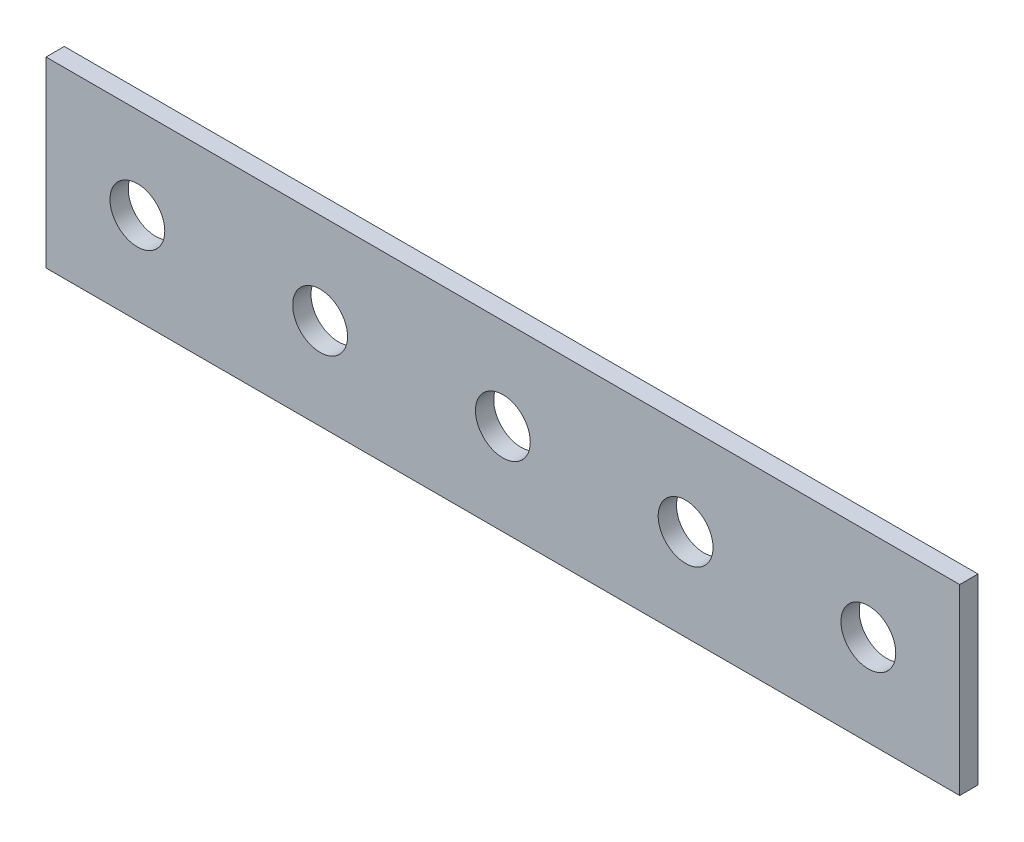
SolidWorks part; units mm, degrees
ref_plane "Front Plane" through (0, 0, 0) normal (0, 0, 1) x (1, 0, 0)
ref_plane "Top Plane" through (0, 0, 0) normal (0, 1, 0) x (1, 0, 0)
ref_plane "Right Plane" through (0, 0, 0) normal (1, 0, 0) x (0, 0, -1)
sketch "Esquisse1" plane through (0, 0, 0) normal (0, 0, 1) x (1, 0, 0)
  line L1 (0, 0) -> (50, 0)
  line L2 (0, 0) -> (0, 10)
  line L3 (0, 10) -> (50, 10)
  line L4 (50, 0) -> (50, 10)
  dimension "D1" = 10
  dimension "D2" = 50
extrude "Boss.-Extru.1" add sketch "Esquisse1" along normal blind 1
sketch "Esquisse2" plane through (0, 0, 1) normal (0, 0, 1) x (1, 0, 0)
  line L0 (50, 10) -> (0, 10) construction
  line L1 (50, 0) -> (50, 10) construction
  circle A0 centre (25, 5) radius 1.5
  point P2 (0, 0)
  point P5 (25, 10)
  point P6 (0, 0)
  point P9 (0, 0)
  point P10 (50, 5)
  dimension "D1" = 3
extrude "Enlèv. mat.-Extru.1" cut sketch "Esquisse2" against normal through all
pattern_linear "Répétition linéaire1" count 3 spacing 10 along (1, 0, 0) of "Enlèv. mat.-Extru.1"
pattern_linear "Répétition linéaire2" count 3 spacing 10 along (-1, 0, 0) of "Enlèv. mat.-Extru.1"
